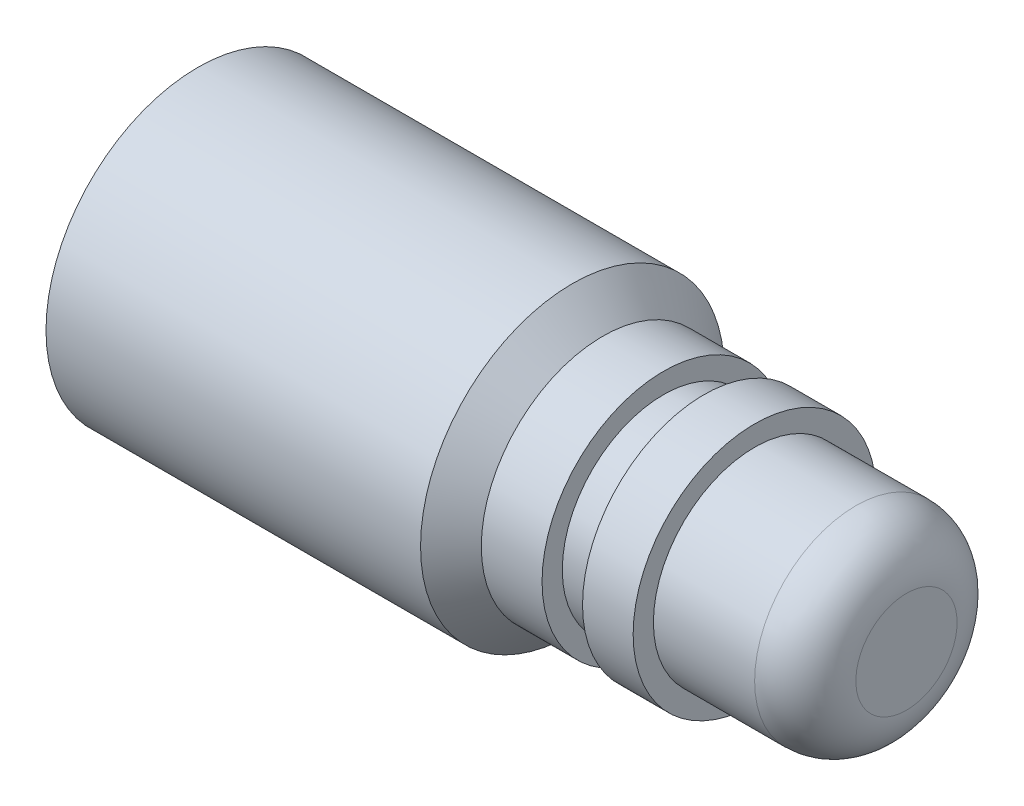
SolidWorks part; units mm, degrees
ref_plane "Přední rovina" through (0, 0, 0) normal (0, 0, 1) x (1, 0, 0)
ref_plane "Vrchní rovina" through (0, 0, 0) normal (0, 1, 0) x (1, 0, 0)
ref_plane "Pravá rovina" through (0, 0, 0) normal (1, 0, 0) x (0, 0, -1)
sketch "Skica1" plane through (0, 0, 0) normal (0, 0, 1) x (1, 0, 0)
  line L0 (-5.4499, 0) -> (79.0225, 0) construction
  line L1 (0, 0) -> (0, 15)
  line L2 (0, 15) -> (40, 15)
  line L3 (40, 15) -> (40, 12)
  line L6 (40, 12) -> (46, 12)
  line L7 (46, 12) -> (46, 10)
  line L8 (46, 10) -> (50, 10)
  line L9 (50, 10) -> (50, 12)
  line L10 (50, 12) -> (55, 12)
  line L11 (55, 12) -> (55, 10)
  line L12 (55, 10) -> (70, 10)
  line L13 (70, 10) -> (70, 0)
  point P5 (46, 11)
  point P8 (79.0225, 0)
  point P9 (52.5, 12)
  point P18 (-5.4499, 0)
  dimension "D1" = 15
  dimension "D2" = 20
  dimension "D3" = 24
  dimension "D4" = 30
  dimension "D5" = 70
  dimension "D6" = 30
  dimension "D7" = 20
  dimension "D8" = 24
revolve "Rotovat1" add sketch "Skica1" angle 360 about L0
fillet "Zaoblit1" radius 5 1 edges at (70, 0, 10)
chamfer "Zkosení1" distance 3 angle 45 1 edges at (40, 0, 15)
